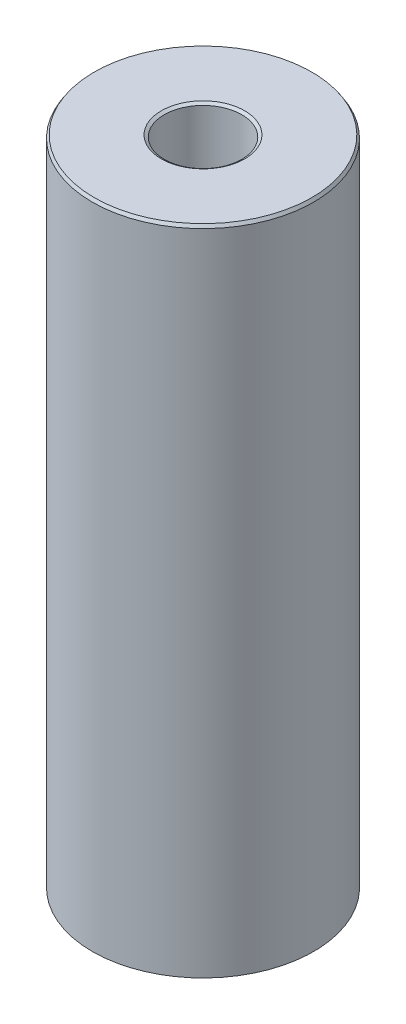
SolidWorks part; units mm, degrees
ref_plane "Front Plane" through (0, 0, 0) normal (0, 0, 1) x (1, 0, 0)
ref_plane "Top Plane" through (0, 0, 0) normal (0, 1, 0) x (1, 0, 0)
ref_plane "Right Plane" through (0, 0, 0) normal (1, 0, 0) x (0, 0, -1)
sketch "Sketch1" plane through (0, 0, 0) normal (0, 1, 0) x (1, 0, 0)
  circle A0 centre (0, 0) radius 7.5
  dimension "SLEEVE_OD" = 15
extrude "Boss-Extrude1" add sketch "Sketch1" along normal blind 44.3036
sketch "Sketch2" plane through (0, 0, 0) normal (0, 1, 0) x (1, 0, 0)
  circle A0 centre (0, 0) radius 2.6246
  dimension "BORE_D" = 5.2492
extrude "Cut-Extrude1" cut sketch "Sketch2" along normal through all
chamfer "Chamfer1" distance 0.2014 angle 32.549 4 edges at (0, 44.3036, 2.6246) (0, 0, 2.6246) (0, 0, 7.5) (0, 44.3036, 7.5) first distance on face at (0, 44.3036, 2.6246) first distance on face at (0, 0, 2.6246) first distance on face at (0, 44.3036, 7.5)
